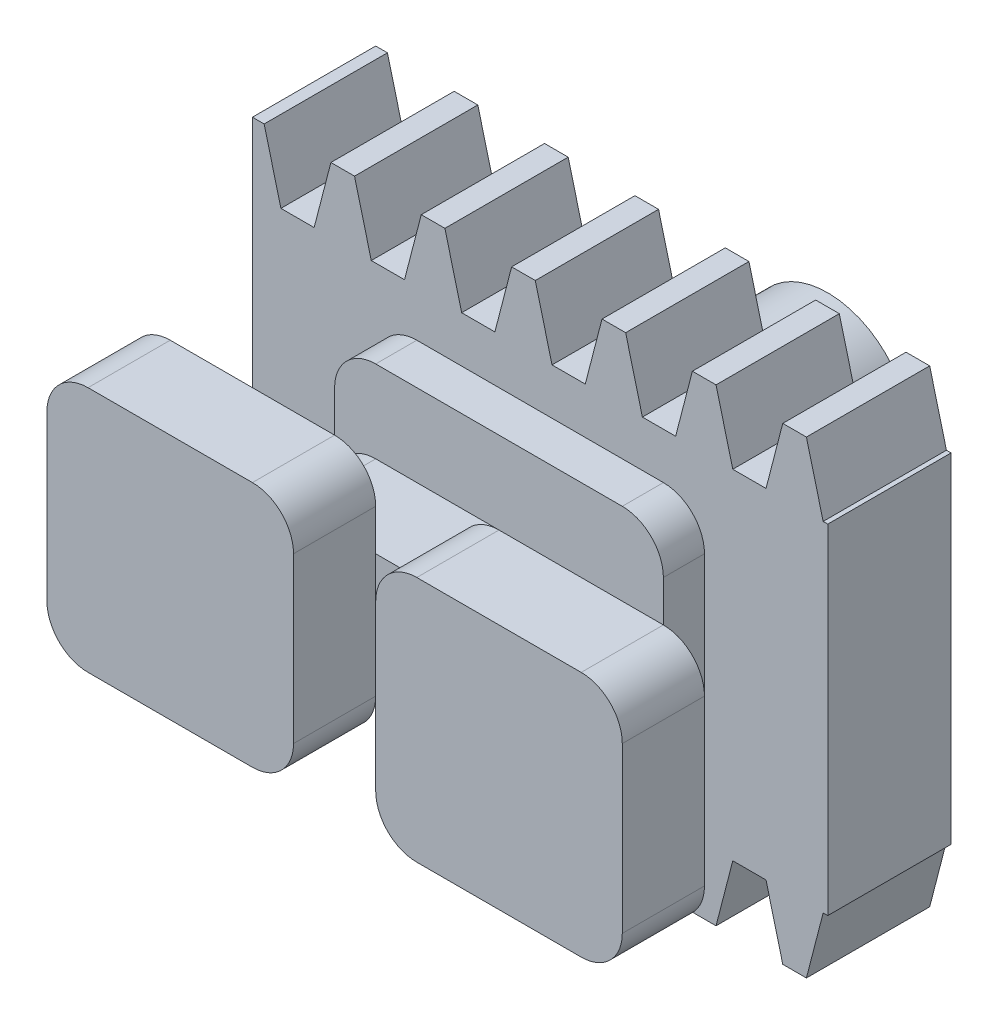
SolidWorks part; units mm, degrees
extrude "Blank" add sketch "BlankSke" against normal blind 3
sketch "BlankSke" plane through (0, 0, 0) normal (0, 0, 1) x (1, 0, 0)
  line L1 (0, 0) -> (25, 0)
  line L2 (0, 0) -> (0, 5.7)
  line L3 (0, 5.7) -> (25, 5.7)
  line L4 (25, 0) -> (25, 5.7)
  dimension "Length" = 25
ref_plane "Plane1" through (0, 0, 0) normal (0, 0, 1) x (1, 0, 0)
ref_plane "Plane2" through (0, 0, 0) normal (0, 1, 0) x (1, 0, 0)
ref_plane "Plane3" through (0, 0, 0) normal (1, 0, 0) x (0, 0, -1)
other "Configuration Table"
sketch "HoldingSke" plane through (0, 0, 0) normal (0, 1, 0) x (1, 0, 0)
  line L0 (0, 0) -> (0.1988, 1.4147)
  line L1 (-15, 0) -> (100, 0) construction
  line L2 (0, 0) -> (-2.1039, 2.3779)
  line L3 (0, 0) -> (-11.863, 4.5341)
  line L4 (0, 0) -> (8.4147, 1.9427)
  line L5 (0, 0) -> (-23.7986, -8.8762)
  line L6 (0, 0) -> (-10.5278, -7.1032)
  line L9 (-67.7845, 28.3722) -> (-43.5808, 34.6317)
  line L10 (-76.2, 3.0779) -> (-71.2, 3.0779)
  line L11 (0, 0) -> (-3, 0)
  line L12 (-76.2, 101.6) -> (-76.173, 101.6)
  line L13 (24.9733, 27.94) -> (52.9518, 28.4284)
  line L14 (24.9733, 27.94) -> (24.9743, 27.94)
  line L15 (24.9733, 27.94) -> (100.4006, 29.5858)
  circle A0 centre (0, 0) radius 19.05
  circle A1 centre (0, 0) radius 2.5
  circle A2 centre (0, 0) radius 12.7
  dimension "Num_teeth" = 13
  dimension "Width" = 3
  dimension "Length" = 25
  dimension "Pitch_height" = 5
sketch "TooCutSkeIll" plane through (0, 0, 0) normal (0, 0, 1) x (1, 0, 0)
  line L0 (-0.8064, 5.679) -> (-0.4386, 4.2569)
  line L1 (-0.2682, 4.125) -> (0.2682, 4.125)
  line L2 (0.4386, 4.2569) -> (0.8064, 5.679)
  line L3 (25, 5.7) -> (0, 5.7) construction
  line L4 (0, 0) -> (0, 64.897) construction
  line L5 (-13.208, 5) -> (12.954, 5) construction
  line L6 (0, 0) -> (25, 0) construction
  line L7 (0.6308, 5) -> (0.6308, 48.7463) construction
  line L8 (-0.6308, 5) -> (-0.6308, 48.7463) construction
  line L9 (0.8335, 5.7) -> (0.8335, 5.7254)
  line L10 (-0.8335, 5.7) -> (-0.8335, 5.7254)
  line L11 (-0.8335, 5.7254) -> (0.8335, 5.7254)
  arc A0 (0.2682, 4.125) -> (0.4386, 4.2569) centre (0.2682, 4.301) ccw
  arc A1 (-0.4386, 4.2569) -> (-0.2682, 4.125) centre (-0.2682, 4.301) ccw
  arc A2 (0.8335, 5.7) -> (0.8064, 5.679) centre (0.8335, 5.672) ccw
  arc A3 (-0.8064, 5.679) -> (-0.8335, 5.7) centre (-0.8335, 5.672) ccw
  dimension "Addendum_plus" = 0.7254
  dimension "Pitch_height" = 5
  dimension "Pressure_angle" = 14.5
  dimension "Gap_width" = 1.2616
  dimension "Dedendum" = 0.875
extrude "ToothCutIll" [suppressed] cut sketch "TooCutSkeIll" against normal through all
sketch "TooCutSkeSim" plane through (0, 0, 0) normal (0, 0, 1) x (1, 0, 0)
  line L0 (0.4045, 4.125) -> (-0.4045, 4.125)
  line L1 (0.8184, 5.7254) -> (0.4045, 4.125)
  line L2 (0, 17.4625) -> (0, 53.467) construction
  line L3 (0.8184, 5.7254) -> (-0.8184, 5.7254)
  line L6 (-0.8184, 5.7254) -> (-0.4045, 4.125)
  line L9 (-0.6308, 5) -> (0.6308, 5) construction
  line L10 (0, 0) -> (25, 0) construction
  line L11 (0.6308, 5) -> (0.6308, 53.467) construction
  line L12 (-0.6308, 5) -> (-0.6308, 53.467) construction
  dimension "Addendum_plus" = 0.7254
  dimension "Pitch_height" = 5
  dimension "Pressure_angle" = 14.5
  dimension "Gap_width" = 1.2616
  dimension "Dedendum" = 0.875
extrude "ToothCutSim" cut sketch "TooCutSkeSim" against normal through all
pattern_linear "TeethCuts" count 13 spacing 2.1991 along (1, 0, 0) of "ToothCutIll", "ToothCutSim"
mirror "镜向1" [suppressed]
mirror "镜向2" about plane through (0, 0, -3) normal (0, -1, 0) of "Blank", "ToothCutSim", "TeethCuts"
sketch "草图1" plane through (0, 0, 0) normal (-1, 0, 0) x (0, 0, 1)
  line L1 (0, 4.125) -> (0, -4.125) construction
  line L4 (-3, 0) -> (0, 0) construction
  line L5 (-3, 4.125) -> (-3, -4.125) construction
  line L7 (0, -3) -> (0, 3)
  line L8 (0, 3) -> (-2, 3.5)
  line L9 (-2, 3.5) -> (-2, -3.5)
  line L10 (0, -3) -> (-2, -3.5)
  point P11 (-2.5, 0)
  point P12 (-2, 0)
  dimension "D1" = 3
  dimension "D2" = 3.5
  dimension "D3" = 2
sketch "草图2" plane through (0, 0, -3) normal (0, 0, -1) x (-1, 0, 0)
  line L0 (0, 0) -> (-25, 0) construction
  line L1 (0, 4.125) -> (0, -4.125) construction
  line L2 (-25, -5.692) -> (-25, 5.692) construction
  circle A0 centre (-12.5, 0) radius 2
  dimension "D1" = 4
extrude "凸台-拉伸1" add sketch "草图2" along normal blind 4
sketch "草图3" plane through (0, 0, -7) normal (0, 0, -1) x (-1, 0, 0)
  circle A0 centre (-12.5, 0) radius 0.5
  dimension "D1" = 1
extrude "切除-拉伸3" cut sketch "草图3" against normal through all
sketch "草图4" plane through (0, 0, -3) normal (0, 0, -1) x (-1, 0, 0)
  line L0 (-12.5, 0) -> (-21.8848, 0) construction
  line L1 (-12.5, 0) -> (-2.5, 0) construction
  line L2 (-21.8848, 2.1496) -> (-21.8848, -2.1496)
  line L3 (-22.3956, 4.125) -> (-22.803, 5.7) construction
  line L4 (-2.5, 4.125) -> (-2.5, -4.125)
  line L6 (-1.7946, -4.125) -> (-2.6036, -4.125) construction
  line L7 (-22.3956, -4.125) -> (-22.803, -5.7) construction
  line L9 (-1.7946, 4.125) -> (-2.6036, 4.125) construction
  line L10 (-21.8848, 2.1496) -> (-21.8848, 5.9598)
  line L11 (-21.8848, 5.9598) -> (-25.6774, 5.9598)
  line L12 (-25.6774, 5.9598) -> (-25.6774, -6.5792)
  line L13 (-25.6774, -6.5792) -> (-21.8848, -6.5792)
  line L14 (-21.8848, -6.5792) -> (-21.8848, -2.1496)
  line L15 (-2.5, 4.125) -> (-2.5, 6.4022)
  line L16 (-2.5, 6.4022) -> (0, 6.4022)
  line L17 (0, 6.4022) -> (0, -6.0736)
  line L18 (0, -6.0736) -> (-2.5, -6.0736)
  line L19 (-2.5, -6.0736) -> (-2.5, -4.125)
  dimension "D2" = 10
extrude "切除-拉伸4" cut sketch "草图4" against normal blind 10
sketch "草图5" plane through (0, 0, 0) normal (0, 0, 1) x (1, 0, 0)
  line L0 (2.5, 2) -> (21.8848, 2)
  line L1 (2.5, 4.125) -> (2.5, -4.125) construction
  line L2 (21.8848, -4.125) -> (21.8848, 4.125) construction
  line L3 (21.8848, 2) -> (21.8848, -2)
  line L4 (21.8848, -2) -> (2.5, -2)
  line L5 (2.5, -2) -> (2.5, 2)
  point P8 (2.5, 0)
  point P9 (21.8848, 0)
  dimension "D1" = 4
sketch "草图6" plane through (0, 0, 0) normal (0, 0, 1) x (1, 0, 0)
  line L0 (1.1742, 0) -> (24.2349, 0) construction
  line L1 (8.5, 1) -> (8.5, -1)
  line L2 (8.5, -1) -> (16.5, -1)
  line L3 (16.5, -1) -> (16.5, 1)
  line L4 (16.5, 1) -> (8.5, 1)
  point P2 (16.5, 0)
  point P4 (12.5, 0)
  point P5 (8.5, 0)
  dimension "D1" = 2
  dimension "D2" = 8
  dimension "D3" = 4
extrude "凸台-拉伸3" add sketch "草图6" along normal blind 3
sketch "草图7" plane through (0, 0, 3) normal (0, 0, 1) x (1, 0, 0)
  line L0 (5.5, 3) -> (11.5, 3)
  line L1 (19.5, 3) -> (19.5, -3)
  line L2 (19.5, -3) -> (13.5, -3)
  line L3 (5.5, -3) -> (5.5, 3)
  line L5 (16.5, 1) -> (8.5, 1) construction
  line L6 (8.5, -1) -> (16.5, -1) construction
  line L7 (8.5, 1) -> (8.5, -1) construction
  line L8 (16.5, -1) -> (16.5, 1) construction
  line L9 (11.5, 3) -> (11.5, -3)
  line L10 (13.5, 3) -> (13.5, -3)
  line L11 (13.5, 3) -> (19.5, 3)
  line L12 (11.5, -3) -> (5.5, -3)
  dimension "D1" = 2
  dimension "D2" = 2
  dimension "D3" = 3
  dimension "D4" = 3
  dimension "D5" = 6
  dimension "D6" = 6
extrude "凸台-拉伸4" add sketch "草图7" along normal blind 2
fillet "圆角1" radius 1 4 edges at (16.5, -1, 1.5) (8.5, -1, 1.5) (16.5, 1, 1.5) (8.5, 1, 1.5)
fillet "圆角2" radius 1 8 edges at (5.5, -3, 4) (5.5, 3, 4) (11.5, 3, 4) (11.5, -3, 4) (13.5, -3, 4) (13.5, 3, 4) (19.5, 3, 4) (19.5, -3, 4)
sketch "草图8" plane through (0, 0, 0) normal (0, 0, 1) x (1, 0, 0)
  line L15 (8.5, 3) -> (8.5, -3)
  line L16 (10.5, 3) -> (6.5, 3) construction
  line L17 (6.5, -3) -> (10.5, -3) construction
  line L18 (8.5, -3) -> (16.5, -3)
  line L19 (14.5, -3) -> (18.5, -3) construction
  line L20 (16.5, -3) -> (16.5, 3)
  line L21 (16.5, 3) -> (8.5, 3)
  line L22 (11.5, -2) -> (11.5, 2) construction
  dimension "D1" = 3
  dimension "D2" = 8
extrude "凸台-拉伸5" add sketch "草图8" along normal blind 1
fillet "圆角5" radius 1 4 edges at (16.5, -3, 0.5) (8.5, -3, 0.5) (8.5, 3, 0.5) (16.5, 3, 0.5)
sketch "草图9" plane through (0, 0, 0) normal (0, 0, 1) x (1, 0, 0)
  line L0 (5.5, 0) -> (5.5, -6.2232)
  line L1 (5.5, 2) -> (5.5, -2) construction
  line L2 (5.5, -6.2232) -> (2.2382, -6.2232)
  line L3 (2.2382, -6.2232) -> (2.2382, 6.2496)
  line L4 (2.2382, 6.2496) -> (5.5, 6.2496)
  line L5 (5.5, 6.2496) -> (5.5, 0)
  line L6 (19.5, 0) -> (19.5, -6.2232)
  line L7 (19.5, -2) -> (19.5, 2) construction
  line L8 (19.5, -6.2232) -> (22.4063, -6.2232)
  line L9 (22.4063, -6.2232) -> (22.4063, 6.2496)
  line L10 (22.4063, 6.2496) -> (19.5, 6.2496)
  line L11 (19.5, 6.2496) -> (19.5, 0)
extrude "切除-拉伸5" cut sketch "草图9" against normal through all
sketch "草图10" plane through (0, 0, -7) normal (0, 0, -1) x (-1, 0, 0)
  circle A0 centre (-12.5, 0) radius 1
extrude "切除-拉伸6" cut sketch "草图10" against normal blind 5.5
equation "' \"Module@HoldingSke\" = 6.35"
equation "' \"Num_teeth@HoldingSke\" = 12"
equation "' \"Ap@HoldingSke\" =  20"
equation "' \"Ap@HoldingSke\" = 20"
equation "' \"Width@HoldingSke\" = 0.25 * 25.4"
equation "' \"Show_teeth@HoldingSke\" = 500"
equation "' \"Backlash@HoldingSke\" = 0.009 * 25.4"
equation "' \"Addendum_fac@HoldingSke\" = 1.0"
equation "' \"Dedendum_fac@HoldingSke\" = 1.25"
equation "' \"Dedendum_add@HoldingSke\" = 0.00005 * 25.4"
equation "' \"Clearance_fac@HoldingSke\" = 0.25"
equation "' \"Pitch_height@HoldingSke\" = 1 * 25.4"
equation "' \"Length@HoldingSke\" = 4.71 * 25.4"
equation "\"Pitch@HoldingSke\" = 1 / \"Module@HoldingSke\""
equation "\"MPH@HoldingSke\" = \"Dedendum_fac@HoldingSke\" / \"Pitch@HoldingSke\" + 2 * \"Dedendum_add@HoldingSke\" + 0.002 * 25.4"
equation "\"MPH@HoldingSke\" = ((sgn( \"MPH@HoldingSke\" - \"Pitch_height@HoldingSke\")+1)*( \"MPH@HoldingSke\" - \"Pitch_height@HoldingSke\"))/2 + \"Pitch_height@HoldingSke\""
equation "\"Blank_height@BlankSke\" = \"Pitch_height@HoldingSke\" + \"Addendum_fac@HoldingSke\"  / \"Pitch@HoldingSke\" "
equation "\"Length@BlankSke\" =  \"Length@HoldingSke\""
equation "\"Face_width@Blank\" = \"Width@HoldingSke\""
equation "\"Pressure_angle@TooCutSkeIll\" = \"Ap@HoldingSke\""
equation "\"Addendum_plus@TooCutSkeIll\" =  \"Addendum_fac@HoldingSke\"  / \"Pitch@HoldingSke\" + 0.001 *25.4"
equation "\"Dedendum@TooCutSkeIll\" = \"Dedendum_fac@HoldingSke\"  / \"Pitch@HoldingSke\""
equation "\"Pitch_height@TooCutSkeIll\" =  \"MPH@HoldingSke\""
equation "\"Gap_width@TooCutSkeIll\" = 3.14159265 / 2 / \"Pitch@HoldingSke\" + 6 * \"Backlash@HoldingSke\""
equation "\"Pressure_angle@TooCutSkeSim\" = \"Ap@HoldingSke\""
equation "\"Addendum_plus@TooCutSkeSim\" =  \"Addendum_fac@HoldingSke\"  / \"Pitch@HoldingSke\" + 0.001 * 25.4"
equation "\"Dedendum@TooCutSkeSim\" = \"Dedendum_fac@HoldingSke\"  / \"Pitch@HoldingSke\""
equation "\"Pitch_height@TooCutSkeSim\" =  \"MPH@HoldingSke\""
equation "\"Gap_width@TooCutSkeSim\" = 3.14159265 / 2 / \"Pitch@HoldingSke\" + 6 * \"Backlash@HoldingSke\""
equation "\"Root_fillet@TooCutSkeIll\" = \"Clearance_fac@HoldingSke\" / \"Pitch@HoldingSke\" + \"Dedendum_add@HoldingSke\""
equation "\"Break_rad@TooCutSkeIll\" = 0.02 / \"Pitch@HoldingSke\" * 2"
equation "\"Linear_pitch@TeethCuts\" = 3.14159265 / \"Pitch@HoldingSke\""
equation "\"Num_teeth@HoldingSke\" = int( ( \"Length@HoldingSke\" + 0 ) / (3.14159265 / \"Pitch@HoldingSke\")) + 0.9999  + 1"
equation " \"Num_teeth@TeethCuts\" = int( \"Show_teeth@HoldingSke\" ) + 1"
equation " \"Num_teeth@TeethCuts\" = ((sgn( \"Num_teeth@TeethCuts\" - \"Num_teeth@HoldingSke\" )-1)*( \"Num_teeth@TeethCuts\" - \"Num_teeth@HoldingSke\" ))/-2+ \"Num_teeth@HoldingSke\""
equation " \"Num_teeth@TeethCuts\" = ((sgn( \"Num_teeth@TeethCuts\" - 2.0)+1)*( \"Num_teeth@TeethCuts\" - 2.0))/2 +2.0"
